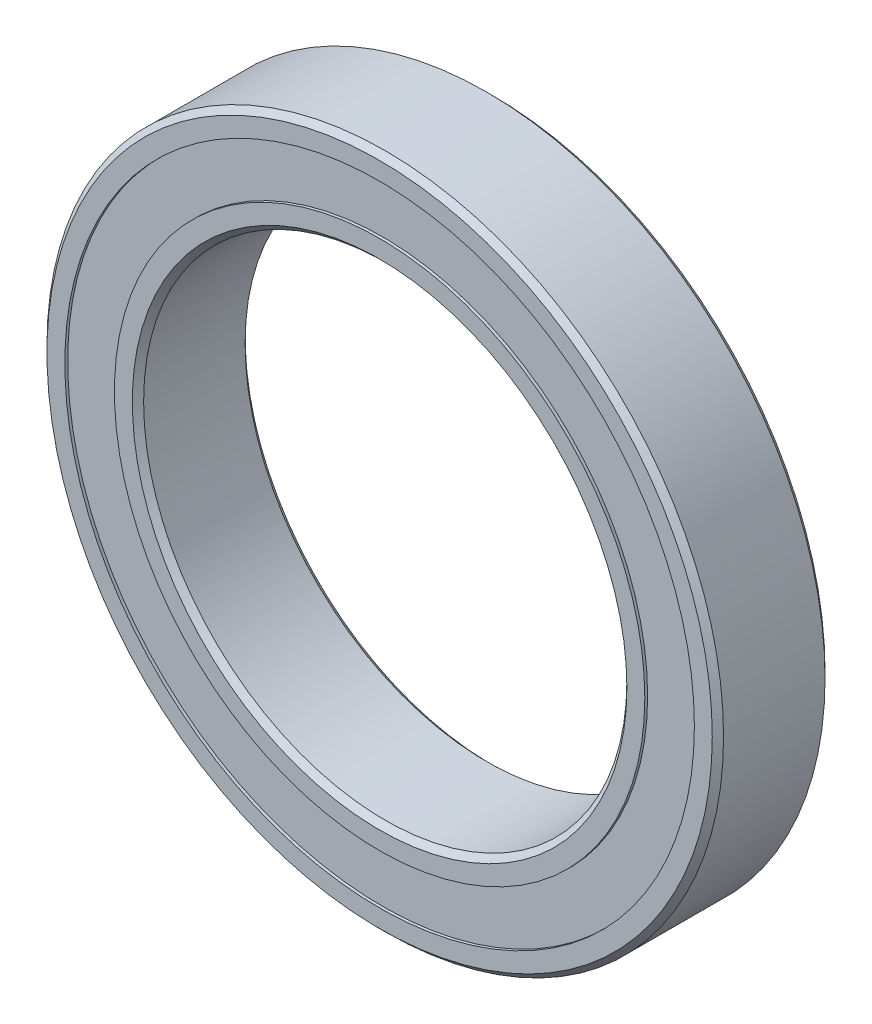
SolidWorks part; units mm, degrees
ref_plane "Front Plane" through (0, 0, 0) normal (0, 0, 1) x (1, 0, 0)
ref_plane "Top Plane" through (0, 0, 0) normal (0, 1, 0) x (1, 0, 0)
ref_plane "Right Plane" through (0, 0, 0) normal (1, 0, 0) x (0, 0, -1)
sketch "Sketch1" plane through (0, 0, 0) normal (1, 0, 0) x (0, 0, -1)
  line L0 (-3.5, 0) -> (3.5, 0) construction
  line L1 (0, 21) -> (0, -21) construction
  line L2 (3.15, 21) -> (-3.15, 21)
  line L3 (-3.15, 21) -> (-3.5, 20.65)
  line L4 (-3.5, 20.65) -> (-3.5, 19.5385)
  line L5 (-3.5, 19.5385) -> (-1.5556, 19.5385)
  line L6 (3.5, 19.5385) -> (1.5556, 19.5385)
  line L7 (3.5, 20.65) -> (3.5, 19.5385)
  line L8 (3.15, 21) -> (3.5, 20.65)
  line L9 (0, 21) -> (0, 18) construction
  line L10 (0, 18) -> (0, 15) construction
  arc A0 (-1.5556, 19.5385) -> (1.5556, 19.5385) centre (0, 18) cw
  point P14 (0, 15)
  dimension "Width" = 7
  dimension "OD" = 42
  dimension "D1" = 45
  dimension "D2" = 0.35
  dimension "Shaft Dia" = 30
  dimension "D3" = 3.1111
  dimension "D4" = 1.5385
revolve "Revolve1" add sketch "Sketch1" angle 360 about L0
sketch "Sketch3" plane through (0, 0, 0) normal (1, 0, 0) x (0, 0, -1)
  line L0 (-3.5, 16.4615) -> (-1.5556, 16.4615)
  line L1 (0, 21) -> (0, -21) construction
  line L2 (-3.5, 20.65) -> (-3.5, 19.5385) construction
  line L3 (-3.5, 16.4615) -> (-3.5, 15.35)
  line L4 (-3.15, 21) -> (-3.5, 20.65) construction
  line L5 (-3.5, 15.35) -> (-3.15, 15)
  line L6 (-3.15, 15) -> (3.15, 15)
  line L7 (3.15, 21) -> (3.15, -21) construction
  line L8 (3.15, 15) -> (3.5, 15.35)
  line L9 (3.5, -20.65) -> (3.5, 20.65) construction
  line L10 (3.5, 15.35) -> (3.5, 16.4615)
  line L11 (3.5, 16.4615) -> (1.5556, 16.4615)
  line L13 (3.15, 21) -> (3.5, 20.65) construction
  arc A0 (1.5556, 19.5385) -> (-1.5556, 19.5385) centre (0, 18) ccw construction
  arc A1 (1.5556, 16.4615) -> (-1.5556, 16.4615) centre (0, 18) cw
revolve "Revolve3" add sketch "Sketch3" angle 360 about L0
sketch "Sketch4" plane through (0, 0, 0) normal (1, 0, 0) x (0, 0, -1)
  line L0 (-2.1878, 18) -> (2.1878, 18)
  arc A2 (-2.1878, 18) -> (2.1878, 18) centre (0, 18) cw
  arc A3 (1.5556, 19.5385) -> (-1.5556, 19.5385) centre (0, 18) ccw construction
revolve "Revolve4" add sketch "Sketch4" angle 360 about L0
ref_axis "Axis1" through (0, 0, -3.5) along (0, 0, 1)
pattern_circular "CirPattern1" count 12 every 30 about axis through (0, 0, -3.5) along (0, 0, 1) of bodies 104
sketch "Sketch5" plane through (0, 0, 0) normal (1, 0, 0) x (0, 0, -1)
  line L0 (-3.5, 19.5385) -> (-1.5556, 19.5385) construction
  line L1 (-3.325, 19.5385) -> (-2.1878, 19.5385)
  line L2 (-3.325, 19.5385) -> (-3.325, 16.4615)
  line L3 (-3.325, 16.4615) -> (-2.1878, 16.4615)
  line L4 (-2.1878, 19.5385) -> (-2.1878, 16.4615)
  line L5 (-3.5, 16.4615) -> (-1.5556, 16.4615) construction
  line L6 (3.5, 19.5385) -> (1.5556, 19.5385) construction
  line L7 (3.325, 19.5385) -> (2.1878, 19.5385)
  line L8 (3.325, 19.5385) -> (3.325, 16.4615)
  line L9 (3.325, 16.4615) -> (2.1878, 16.4615)
  line L10 (2.1878, 19.5385) -> (2.1878, 16.4615)
  line L11 (3.5, 16.4615) -> (1.5556, 16.4615) construction
  line L12 (-3.15, 21) -> (-3.5, 20.65) construction
  point P18 (-3.325, 20.825)
revolve "Revolve5" add sketch "Sketch5" angle 360 about L0
equation "\"D2@Sketch1\" = \"Width@Sketch1\"*.05"
equation "\"D3@Sketch1\" = \"Width@Sketch1\"/2.25"
equation "\"D4@Sketch1\" = (((\"OD@Sketch1\"-\"Width@Sketch1\")/2)/3.25)/3.5"
equation "\"D2@CirPattern1\" = 360/\"Balls@CirPattern1\""
